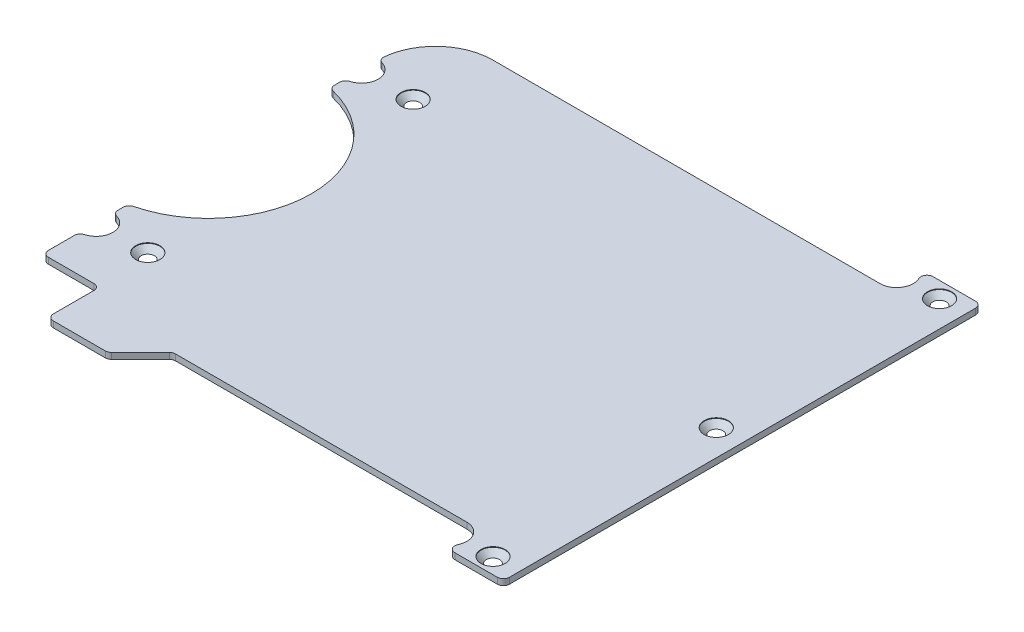
SolidWorks part; units mm, degrees
ref_plane "Front Plane" through (0, 0, 0) normal (0, 0, 1) x (1, 0, 0)
ref_plane "Top Plane" through (0, 0, 0) normal (0, 1, 0) x (1, 0, 0)
ref_plane "Right Plane" through (0, 0, 0) normal (1, 0, 0) x (0, 0, -1)
sketch "Sketch1" plane through (0, 0, 0) normal (0, 1, 0) x (1, 0, 0)
  line L0 (0, 30.3854) -> (0, -26.0557) construction
  line L1 (-19.0199, 0) -> (15.6179, 0) construction
  line L2 (-73.452, 57.1764) -> (-73.452, -39.7909) construction
  line L3 (0, 34.13) -> (-63.992, 34.13)
  line L4 (0, -34.13) -> (-48.582, -34.13)
  line L5 (-73.452, 19.17) -> (-73.452, 16.6626)
  line L6 (-48.582, -34.13) -> (-53.952, -39.5)
  line L7 (-63.952, -34.13) -> (-63.952, -39.5)
  line L8 (-73.452, -19.17) -> (-73.452, -16.6626)
  line L9 (11.4, 39.5) -> (11.4, -39.5)
  line L10 (11.4, 39.5) -> (0.8355, 39.5)
  line L11 (11.4, -39.5) -> (0.8355, -39.5)
  line L12 (-48.582, -34.13) -> (-73.452, -34.13) construction
  line L13 (-63.952, -39.5) -> (-53.952, -39.5)
  line L14 (-73.452, -24.67) -> (-73.452, -30.8)
  line L15 (-63.952, 0) -> (-63.952, -34.13) construction
  line L16 (-73.452, -30.8) -> (-63.952, -30.8)
  line L17 (-63.952, -30.8) -> (-63.952, -34.13)
  line L18 (2.75, 36.88) -> (2.75, -36.88) construction
  line L19 (2.75, 36.88) -> (11.4, 36.88) construction
  line L20 (-73.452, 21.92) -> (11.4, 21.92) construction
  line L21 (7.075, 36.88) -> (7.075, -36.88) construction
  circle A0 centre (0, 36.88) radius 2.5
  circle A1 centre (0, -36.88) radius 2.5
  circle A2 centre (-73.452, 21.92) radius 2.5
  circle A3 centre (-73.452, -21.92) radius 2.5
  circle A4 centre (-76.822, 0) radius 16
  circle A5 centre (-73.452, 21.92) radius 2.75
  circle A6 centre (-76.822, 0) radius 17
  circle A7 centre (-73.452, -21.92) radius 2.75
  circle A8 centre (0, 36.88) radius 2.75
  circle A9 centre (0, -36.88) radius 2.75
  arc A10 (-73.452, 24.67) -> (-63.992, 34.13) centre (-63.992, 24.67) cw
  circle A11 centre (7.075, 36.88) radius 1
  circle A12 centre (7.075, -36.88) radius 1
  circle A13 centre (-64.925, 21.92) radius 1
  circle A14 centre (-64.925, -21.92) radius 1
  circle A15 centre (7.075, 0) radius 1
  point P39 (11.4, 0)
  dimension "D2" = 5
  dimension "D3" = 43.84
  dimension "D5" = 32
  dimension "D16" = 2
  dimension "D1" = 73.76
  dimension "D4" = 74.96
  dimension "D6" = 3.37
  dimension "D12" = 79
  dimension "D13" = 11.4
  dimension "D9" = 10
  dimension "D10" = 45
  dimension "D11" = 5.37
  dimension "D14" = 8.7
  dimension "D15" = 9.5
  dimension "D17" = 72
  dimension "D7" = 0.25
  dimension "D8" = 1
extrude "Base shape" add sketch "Sketch1" along normal mid plane 1 contours A9 L11 L9 L10 A8 L3 A5 L5 A6 L8 A7 region at (-27.9104, 0, 0.3767)
fillet "Fillets" radius 1 15 edges at (-48.582, 0, 34.13) (-53.952, 0, 39.5) (-73.452, 0, -24.67) (-73.452, 0, -19.17) (-73.452, 0, -16.6626) (-73.452, 0, 24.67) (-73.452, 0, 19.17) (-73.452, 0, 16.6626) (-73.452, 0, 30.8) (-63.952, 0, 30.8) (0.8355, 0, -39.5) (0.8355, 0, 39.5) (11.4, 0, -39.5) (11.4, 0, 39.5) (-63.952, 0, 39.5)
hole_wizard "M2 countersunks" positions "Sketch2" profile "Sketch3" countersink size "M2" standard "ANSI Metric" end condition through all
sketch "Sketch2" plane through (0, -0.5, 0) normal (0, -1, 0) x (-1, 0, 0)
  point P0 (-7.075, 36.88)
  point P3 (-7.075, -36.88)
  point P6 (64.925, 21.92)
  point P9 (64.925, -21.92)
  point P13 (-7.075, 0)
sketch "Sketch3" plane through (7.075, -0.5, -36.88) normal (1, 0, 0) x (0, 0, -1)
  line L0 (0, 0) -> (0, 1)
  line L1 (0, 1) -> (1, 1)
  line L2 (1, 1) -> (1, 1.1)
  line L3 (1, 1.1) -> (2, 0.1)
  line L4 (2, 0.1) -> (2, 0)
  line L6 (2, 0) -> (0, 0)
  line L7 (-1, 1.1) -> (-2, 0.1) construction
  line L11 (0, -6.35) -> (0, 107.95) construction
  dimension "Thru Hole Dia." = 2
  dimension "Thru Hole Depth" = 1
  dimension "C'Sink Dia." = 4
  dimension "C'Sink Angle" = 90
  dimension "Head Clearance" = 0.1
mirror "Mirror1" about plane through (0, 0, 0) normal (0, 1, 0) of bodies 105
delete or keep bodies "Body-Delete/Keep 1" type delete bodies bodies 105
